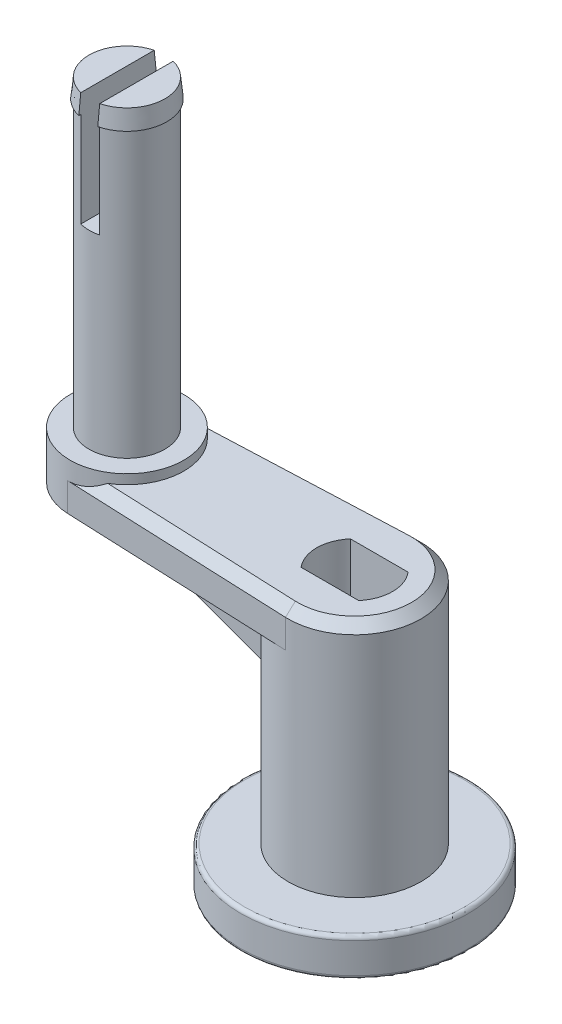
SolidWorks part; units mm, degrees
ref_plane "前视基准面" through (0, 0, 0) normal (0, 0, 1) x (1, 0, 0)
ref_plane "上视基准面" through (0, 0, 0) normal (0, 1, 0) x (1, 0, 0)
ref_plane "右视基准面" through (0, 0, 0) normal (1, 0, 0) x (0, 0, -1)
sketch "草图1" plane through (0, 0, 0) normal (0, 1, 0) x (1, 0, 0)
  circle A0 centre (0, 0) radius 6
  dimension "D1" = 12
extrude "凸台-拉伸1" add sketch "草图1" along normal blind 2
sketch "草图2" plane through (0, 2, 0) normal (0, 1, 0) x (1, 0, 0)
  circle A0 centre (0, 0) radius 3.5
  dimension "D1" = 7
extrude "凸台-拉伸2" add sketch "草图2" along normal blind 12.5
sketch "草图3" plane through (0, 14.5, 0) normal (0, 1, 0) x (1, 0, 0)
  line L0 (0, 0) -> (-12, 0) construction
  line L1 (-12.125, 2.9974) -> (-0.1458, 3.497)
  line L2 (-12.125, -2.9974) -> (-0.1458, -3.497)
  arc A0 (-12.125, 2.9974) -> (-12.125, -2.9974) centre (-12, 0) ccw
  circle A1 centre (0, 0) radius 3.5 construction
  arc A2 (-0.1458, -3.497) -> (-0.1458, 3.497) centre (0, 0) ccw
  dimension "D2" = 6
  dimension "D1" = 12
extrude "凸台-拉伸3" add sketch "草图3" against normal blind 2.5
sketch "草图4" plane through (0, 0, 0) normal (0, 0, 1) x (1, 0, 0)
  line L0 (-15, 12) -> (-14.2, 12) construction
  line L1 (-15, 12) -> (-12.125, 12) construction
  line L2 (-14.2, 12) -> (-3.2, 8)
  line L3 (-3.2, 8) -> (-3.2, 12) construction
  line L4 (-3.5, 12) -> (-0.1458, 12) construction
  line L5 (-3.2, 12) -> (-14.2, 12)
  line L6 (-3.2, 12) -> (-0.2, 12)
  line L7 (-12.125, 12) -> (-0.1458, 12) construction
  line L8 (-0.2, 12) -> (-0.2, 6.9091)
  line L9 (-3.2, 8) -> (-0.2, 6.9091)
  dimension "D1" = 0.8
  dimension "D2" = 11
  dimension "D3" = 4
  dimension "D4" = 3
extrude "凸台-拉伸4" add sketch "草图4" along normal blind 0.5 and the other way blind 0.5
sketch "草图5" plane through (0, 14.5, 0) normal (0, 1, 0) x (1, 0, 0)
  circle A0 centre (-12, 0) radius 3
extrude "凸台-拉伸5" add sketch "草图5" along normal blind 0.5
sketch "草图6" plane through (0, 15, 0) normal (0, 1, 0) x (1, 0, 0)
  circle A0 centre (-12, 0) radius 2
  dimension "D1" = 4
extrude "凸台-拉伸6" add sketch "草图6" along normal blind 16
sketch "草图7" plane through (0, 0, 0) normal (0, 0, 1) x (1, 0, 0)
  line L0 (-12, 31) -> (-14, 31)
  line L1 (-10, 31) -> (-14, 31) construction
  line L2 (-14, 31) -> (-14.1, 30)
  line L3 (-14.1, 30) -> (-12, 30)
  line L4 (-12, 30) -> (-12, 31)
  dimension "D1" = 1
  dimension "D2" = 2.1
  dimension "D3" = 2
revolve "旋转1" add sketch "草图7" angle 360 about L4
sketch "草图8" plane through (0, 31, 0) normal (0, 1, 0) x (1, 0, 0)
  line L0 (-11.5, 3) -> (-12.5, 3)
  line L1 (-11.5, 3) -> (-11.5, -3)
  line L2 (-12.5, 3) -> (-12.5, -3)
  line L3 (-11.5, -3) -> (-12.5, -3)
  line L4 (-11.5, 3) -> (-12.5, -3) construction
  line L5 (-12.5, 3) -> (-11.5, -3) construction
  point P1 (-12, 0)
  dimension "D1" = 0.5
  dimension "D2" = 6
extrude "切除-拉伸1" cut sketch "草图8" against normal blind 6
sketch "草图9" plane through (0, 14.5, 0) normal (0, 1, 0) x (1, 0, 0)
  line L1 (1.5199, -1.3) -> (-1.5199, -1.3)
  line L2 (1.5199, 1.3) -> (-1.5199, 1.3)
  arc A0 (-1.5199, 1.3) -> (-1.5199, -1.3) centre (0, 0) ccw
  arc A1 (1.5199, -1.3) -> (1.5199, 1.3) centre (0, 0) ccw
  dimension "D1" = 4
  dimension "D2" = 1.3
  dimension "D3" = 1.3
extrude "切除-拉伸2" cut sketch "草图9" against normal through all
fillet "圆角1" radius 0.2 2 edges at (0, 0, 6) (0, 2, 6)
chamfer "倒角1" distance 0.5 angle 45 6 edges at (-6.1354, 12, 3.2472) (-15, 12, 0) (-6.1354, 12, -3.2472) (3.5, 14.5, 0)
